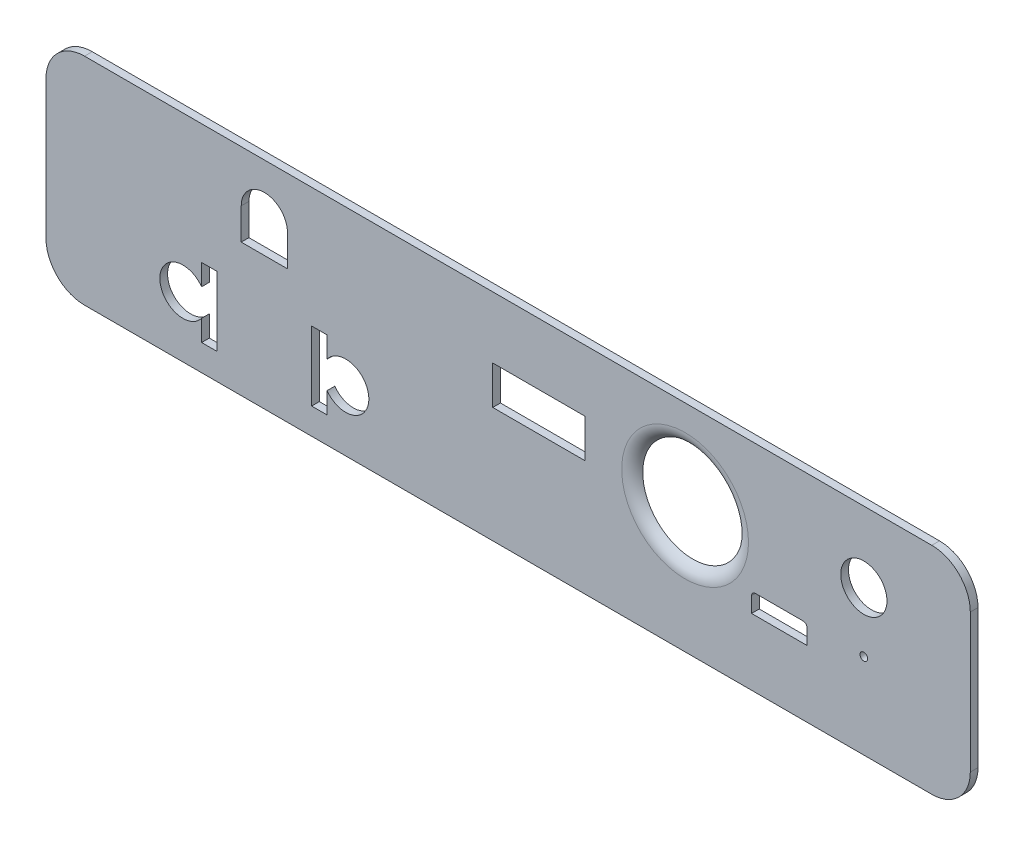
SolidWorks part; units mm, degrees
ref_plane "Front Plane" through (0, 0, 0) normal (0, 0, 1) x (1, 0, 0)
ref_plane "Top Plane" through (0, 0, 0) normal (0, 1, 0) x (1, 0, 0)
ref_plane "Right Plane" through (0, 0, 0) normal (1, 0, 0) x (0, 0, -1)
sketch "Sketch4" plane through (0, 0, 0) normal (0, 0, 1) x (1, 0, 0)
  line L0 (0, 0.0525) -> (0, 26.8296) construction
  line L2 (0, 14.0525) -> (55, 14.0525)
  line L3 (0, 14.0525) -> (-55, 14.0525)
  line L4 (0, 0.0525) -> (70.3724, 0.0525) construction
  line L5 (73.8857, 0.0525) -> (-73.8857, 0.0525) construction
  line L6 (0, -13.9475) -> (55, -13.9475)
  line L7 (0, -13.9475) -> (-55, -13.9475)
  line L8 (-60, 9.0525) -> (-60, -8.9475)
  line L9 (60, 9.0525) -> (60, -8.9475)
  arc A16 (55, 14.0525) -> (60, 9.0525) centre (55, 9.0525) cw
  arc A17 (55, -13.9475) -> (60, -8.9475) centre (55, -8.9475) ccw
  arc A18 (-55, -13.9475) -> (-60, -8.9475) centre (-55, -8.9475) cw
  arc A19 (-55, 14.0525) -> (-60, 9.0525) centre (-55, 9.0525) ccw
extrude "Boss-Extrude1" add sketch "Sketch4" along normal blind 1 contours L3 A19 L8 A18 L7 L6 A17 L9 A16 L2 region at (0, 0.0525, 0)
sketch "Sketch11" plane through (0, 0, 1) normal (0, 0, 1) x (1, 0, 0)
  line L0 (-60, 9.0525) -> (-60, -8.9475) construction
  line L1 (55, 14.0525) -> (-55, 14.0525) construction
  line L11 (10, 6.0525) -> (-2, 6.0525)
  line L12 (10, 6.0525) -> (10, 1.0525)
  line L13 (10, 1.0525) -> (-2, 1.0525)
  line L14 (-2, 6.0525) -> (-2, 1.0525)
  dimension "D1" = 58
  dimension "D4" = 5
  dimension "D2" = 8
  dimension "D3" = 12
extrude "Cut-Extrude7" cut sketch "Sketch11" against normal blind 10
sketch "Sketch12" plane through (0, 0, 1) normal (0, 0, 1) x (1, 0, 0)
  line L1 (38.3001, -2.8091) -> (32.1001, -2.8091)
  line L2 (38.8001, -3.3091) -> (38.8001, -5.3091)
  line L3 (38.8001, -5.3091) -> (31.6001, -5.3091)
  line L4 (31.6001, -3.3091) -> (31.6001, -5.3091)
  arc A0 (32.1001, -2.8091) -> (31.6001, -3.3091) centre (32.1001, -3.3091) ccw
  arc A1 (38.3001, -2.8091) -> (38.8001, -3.3091) centre (38.3001, -3.3091) cw
  point P9 (38.8001, -2.8091)
sketch "Sketch13" plane through (0, 0, 1) normal (0, 0, 1) x (1, 0, 0)
  circle A0 centre (46.1802, 4.8788) radius 3
  dimension "D1" = 6
extrude "Cut-Extrude9" cut sketch "Sketch13" against normal blind 10
sketch "Sketch21" plane through (0, 0, 1) normal (0, 0, 1) x (1, 0, 0)
  circle A1 centre (22.9724, 2.4858) radius 6.5
  dimension "D1" = 13
extrude "Cut-Extrude10" cut sketch "Sketch12" against normal blind 10
extrude "Cut-Extrude11" cut sketch "Sketch21" against normal blind 10
sketch "Sketch22" plane through (0, 0, 0) normal (0, 0, 1) x (1, 0, 0)
  line L0 (-39.7948, -7.8126) -> (-39.7948, -10.5459)
  line L1 (-25.5107, -1.5459) -> (-23.5107, -1.5459)
  line L2 (-25.5107, -1.5459) -> (-25.5107, -10.5459)
  line L3 (-25.5107, -10.5459) -> (-23.5107, -10.5459)
  line L4 (-23.5107, -1.5459) -> (-23.5107, -4.2792)
  line L5 (-39.7948, -1.5459) -> (-39.7948, -4.2792)
  line L6 (-37.7948, -10.5459) -> (-39.7948, -10.5459)
  line L7 (-37.7948, -1.5459) -> (-37.7948, -10.5459)
  line L8 (-31.6527, 3.3135) -> (-34.6527, 3.3135)
  line L9 (-31.6527, 3.3135) -> (-28.6527, 3.3135)
  line L10 (-34.6527, 3.3135) -> (-34.6527, 7.3979)
  line L11 (-28.6527, 7.3979) -> (-28.6527, 3.3135)
  line L12 (-37.7948, -1.5459) -> (-39.7948, -1.5459)
  line L13 (-23.5107, -7.8126) -> (-23.5107, -10.5459)
  line L14 (-31.6527, 7.3979) -> (-31.6527, -26.558) construction
  arc A0 (-23.5107, -7.8126) -> (-23.5107, -4.2792) centre (-21.0861, -6.0459) ccw
  arc A1 (-39.7948, -7.8126) -> (-39.7948, -4.2792) centre (-42.2194, -6.0459) cw
  arc A2 (-28.6527, 7.3979) -> (-34.6527, 7.3979) centre (-31.6527, 7.3979) ccw
  dimension "D4" = 3
  dimension "D1" = 2
  dimension "D2" = 9
extrude "Cut-Extrude17" cut sketch "Sketch22" against normal blind 10 and the other way blind 10
sketch "Sketch23" plane through (0, 0, 0) normal (0, 0, -1) x (-1, 0, 0)
  line L1 (-56.1282, 3.148) -> (-54.1282, 3.148)
  line L2 (-56.1282, 3.148) -> (-56.1282, -0.852)
  line L3 (-56.1282, -0.852) -> (-54.1282, -0.852)
  line L4 (-54.1282, 3.148) -> (-54.1282, -0.852)
extrude "Boss-Extrude2" add sketch "Sketch23" along normal blind 3
sketch "Sketch24" plane through (0, 0, 0) normal (0, 0, -1) x (-1, 0, 0)
  line L0 (56.13, 3.148) -> (56.13, -0.852) construction
  line L1 (54.13, 3.148) -> (56.13, 3.148)
  line L2 (54.13, 3.148) -> (54.13, -0.8012)
  line L3 (54.13, -0.8012) -> (56.13, -0.8012)
  line L4 (56.13, 3.148) -> (56.13, -0.8012)
extrude "Boss-Extrude3" add sketch "Sketch24" along normal blind 3
fillet "Fillet1" radius 2 1 edges at (29.4724, 2.4858, 1)
sketch "Sketch25" plane through (0, 0, 1) normal (0, 0, 1) x (1, 0, 0)
  line L0 (46.1802, 4.8788) -> (46.1802, -10.778) construction
  line L1 (55, -13.9475) -> (-55, -13.9475) construction
  circle A0 centre (46.1802, -2.8775) radius 0.5
  dimension "D1" = 11.07
extrude "Cut-Extrude18" cut sketch "Sketch25" against normal blind 10
